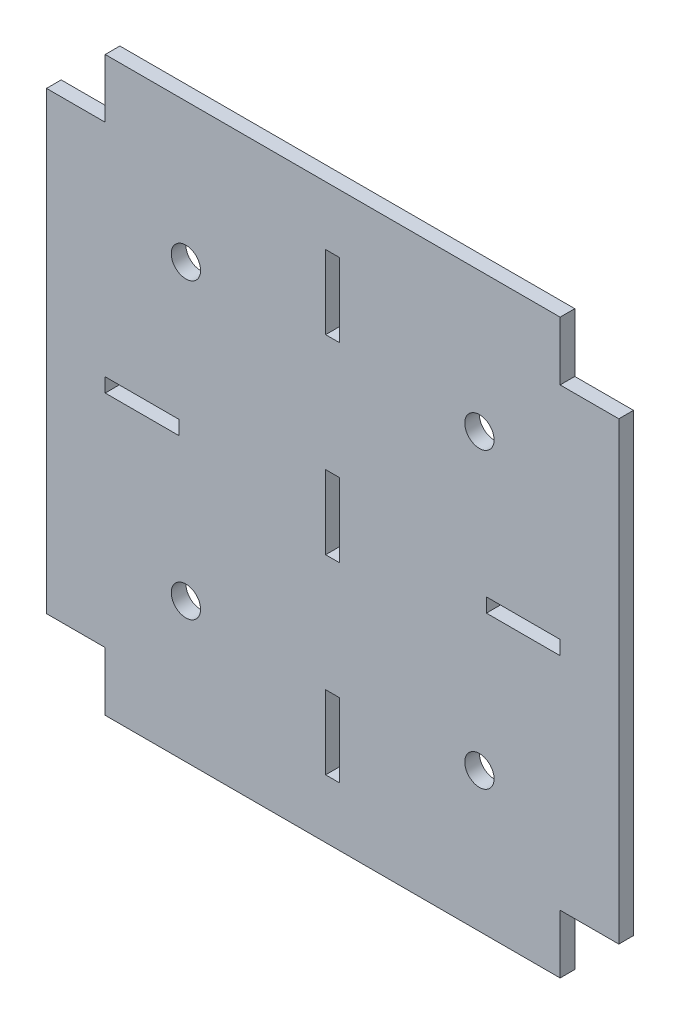
SolidWorks part; units mm, degrees
ref_plane "前基準面" through (0, 0, 0) normal (0, 0, 1) x (1, 0, 0)
ref_plane "上基準面" through (0, 0, 0) normal (0, 1, 0) x (1, 0, 0)
ref_plane "右基準面" through (0, 0, 0) normal (1, 0, 0) x (0, 0, -1)
sketch "草圖1" plane through (0, 0, 0) normal (0, 0, 1) x (1, 0, 0)
  line L0 (0, 0) -> (0, 31.2574) construction
  line L1 (-31, 39) -> (31, 39)
  line L2 (-39, 31) -> (-39, -31)
  line L3 (-31, -39) -> (31, -39)
  line L4 (39, 31) -> (39, -31)
  line L5 (-0.96, -20.95) -> (0.96, -20.95)
  line L6 (-0.96, 31) -> (0.96, 31)
  line L7 (-39, 31) -> (-31, 31)
  line L8 (-31, 39) -> (-31, 31)
  line L9 (-0.96, 31) -> (-0.96, 20.95)
  line L10 (-0.96, 20.95) -> (0.96, 20.95)
  line L11 (39, 31) -> (31, 31)
  line L12 (31, 39) -> (31, 31)
  line L13 (0.96, 31) -> (0.96, 20.95)
  line L14 (-31, 0.96) -> (-20.95, 0.96)
  line L15 (-39, -31) -> (-31, -31)
  line L16 (-31, -39) -> (-31, -31)
  line L17 (-31, 0.96) -> (-31, -0.96)
  line L18 (-31, -0.96) -> (-20.95, -0.96)
  line L19 (39, -31) -> (31, -31)
  line L20 (31, -39) -> (31, -31)
  line L21 (0, 0) -> (-54.2411, 0) construction
  line L22 (-20.95, 0.96) -> (-20.95, -0.96)
  line L23 (0.96, -31) -> (0.96, -20.95)
  line L24 (-0.96, -31) -> (0.96, -31)
  line L25 (-0.96, -31) -> (-0.96, -20.95)
  line L26 (31, 0.96) -> (31, -0.96)
  line L27 (20.95, 0.96) -> (20.95, -0.96)
  line L28 (31, 0.96) -> (20.95, 0.96)
  line L29 (31, -0.96) -> (20.95, -0.96)
  line L31 (-0.96, 5.025) -> (0.96, 5.025)
  line L32 (-0.96, 5.025) -> (-0.96, -5.025)
  line L33 (-0.96, -5.025) -> (0.96, -5.025)
  line L34 (0.96, 5.025) -> (0.96, -5.025)
  circle A0 centre (-20, 20) radius 2
  circle A1 centre (20, 20) radius 2
  circle A2 centre (20, -20) radius 2
  circle A3 centre (-20, -20) radius 2
  point P4 (39, 0)
  point P6 (0, 39)
  point P36 (-105.1594, 8.7956)
  dimension "D11" = 4
  dimension "D1" = 78
  dimension "D2" = 62
  dimension "D3" = 62
  dimension "D4" = 78
  dimension "D5" = 1.92
  dimension "D6" = 10.05
  dimension "D9" = 20
  dimension "D10" = 20
  dimension "D14" = 40
  dimension "D15" = 40
  dimension "D12" = 2
  dimension "D13" = 2
extrude "填料-伸長1" add sketch "草圖1" along normal blind 2
